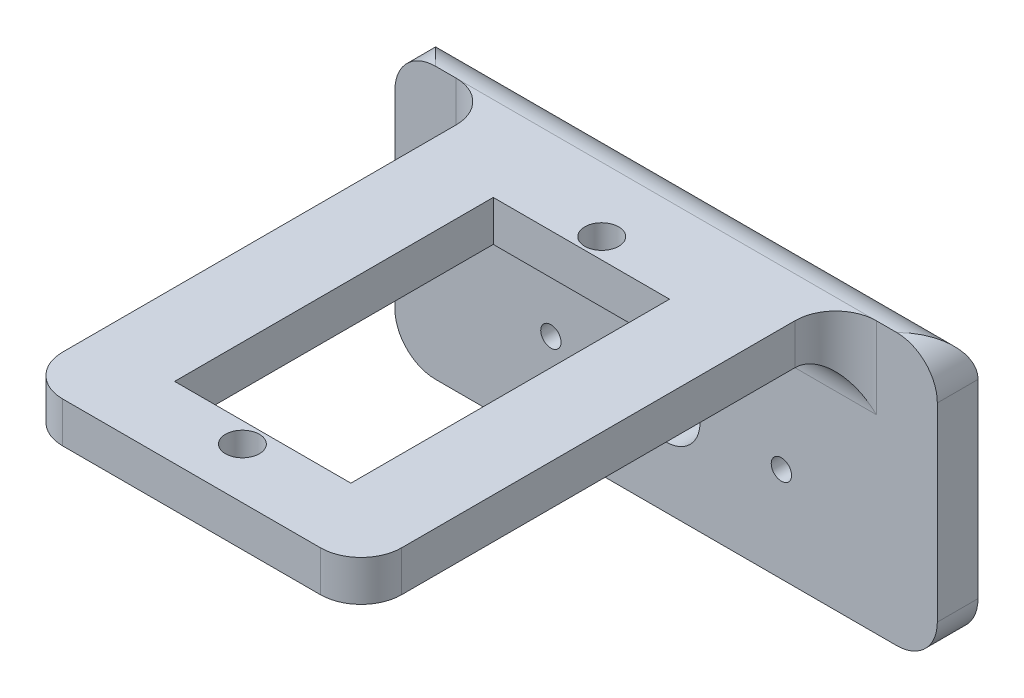
SolidWorks part; units mm, degrees
ref_plane "Plano frontal" through (0, 0, 0) normal (0, 0, 1) x (1, 0, 0)
ref_plane "Plano superior" through (0, 0, 0) normal (0, 1, 0) x (1, 0, 0)
ref_plane "Plano direito" through (0, 0, 0) normal (1, 0, 0) x (0, 0, -1)
sketch "Esboço1" plane through (0, 0, 0) normal (0, 0, 1) x (1, 0, 0)
  line L13 (-20, -12) -> (20, -12)
  line L14 (-20, -12) -> (-20, 8)
  line L15 (-20, 8) -> (20, 8)
  line L16 (20, -12) -> (20, 8)
  arc A12 (-2.4269, 0.6) -> (-2.4269, -0.6) centre (0, 0) ccw
  point P29 (0, 8)
  dimension "D8" = 5
  dimension "D3" = 20
  dimension "D4" = 40
  dimension "D5" = 12
extrude "Ressalto-extrusão1" add sketch "Esboço1" against normal blind 1 contours L13 L16 L15 L14 region at (0, -2, 0)
sketch "Esboço2" plane through (0, 0, 0) normal (0, 0, 1) x (1, 0, 0)
  line L0 (-20, 8) -> (20, 8) construction
  circle A0 centre (0, -5) radius 2.5
  circle A4 centre (-8.5, -5) radius 0.75
  point P6 (0, 0)
  dimension "D1" = 13
  dimension "D2" = 5
  dimension "D3" = 1.5
  dimension "D4" = 8.5
sketch "Esboço3" plane through (0, 0, 0) normal (0, 0, 1) x (1, 0, 0)
  line L1 (-20, -12) -> (20, -12)
  line L2 (-20, -12) -> (-20, 8)
  line L3 (-20, 8) -> (20, 8)
  line L4 (20, -12) -> (20, 8)
extrude "Ressalto-extrusão2" add sketch "Esboço3" along normal blind 2
extrude "Corte-extrusão1" cut sketch "Esboço2" along normal up to surface and the other way up to surface up to face at (0, -2, 2) other way up to face at (0, -2, -1)
sketch "Esboço4" plane through (0, 8, 0) normal (0, 1, 0) x (1, 0, 0)
  line L0 (20, -2) -> (-20, -2) construction
  line L1 (6.5, -31.75) -> (-6.5, -31.75)
  line L2 (6.5, -31.75) -> (6.5, -8.25)
  line L3 (6.5, -8.25) -> (-6.5, -8.25)
  line L4 (-6.5, -31.75) -> (-6.5, -8.25)
  line L5 (-20, 1) -> (20, 1) construction
  line L6 (12.5, -2) -> (-12.5, -2)
  line L7 (12.5, -2) -> (12.5, -37)
  line L8 (12.5, -37) -> (-12.5, -37)
  line L9 (-12.5, -2) -> (-12.5, -37)
  line L10 (-12.5, -2) -> (12.5, -2)
  line L11 (-12.5, -2) -> (-12.5, 1)
  line L12 (-12.5, 1) -> (12.5, 1)
  line L13 (12.5, -2) -> (12.5, 1)
  circle A0 centre (0, -6.75) radius 1.25
  circle A1 centre (0, -33.25) radius 1.25
  point P6 (0, -31.75)
  point P13 (0, -2)
  point P14 (0, -37)
  line M5 (-20, -2) -> (20, -2)
  line M7 (20, 1) -> (-20, 1)
  dimension "D6" = 4.75
  dimension "D7" = 2.5
  dimension "D8" = 26.5
  dimension "D1" = 6.25
  dimension "D2" = 23.5
  dimension "D3" = 13
  dimension "D4" = 25
  dimension "D5" = 35
extrude "Ressalto-extrusão3" add sketch "Esboço4" against normal blind 3 contours L13 L11 M5 M7 | L9 L8 L7 L1 L4 L3 L2 M5 region at (12.0699, 8, 19.5) region at (0, 8, 0.5)
mirror "Mirror1" about plane through (0, 0, 0) normal (1, 0, 0) of "Corte-extrusão1"
fillet "Fillet2" radius 3 10 edges at (0, 8, -1) (20, 8, 0.5) (20, -12, 0.5) (-20, -12, 0.5) (-20, 8, 0.5) (12.5, 6.5, 37) (-12.5, 6.5, 37) (12.5, 6.5, 2) (0, 5, 2) (-12.5, 6.5, 2)
